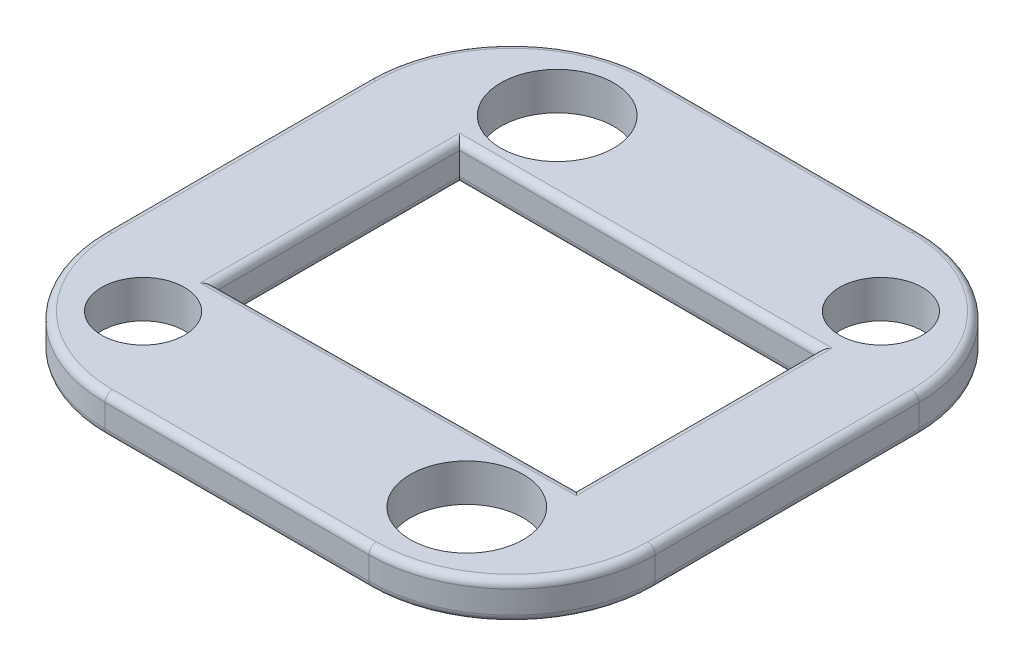
SolidWorks part; units mm, degrees
ref_plane "Front Plane" through (0, 0, 0) normal (0, 0, 1) x (1, 0, 0)
ref_plane "Top Plane" through (0, 0, 0) normal (0, 1, 0) x (1, 0, 0)
ref_plane "Right Plane" through (0, 0, 0) normal (1, 0, 0) x (0, 0, -1)
sketch "Sketch1" plane through (0, 0, 0) normal (0, 1, 0) x (1, 0, 0)
  line L0 (27.0139, 60) -> (54.7461, 60)
  line L1 (20, 0) -> (55, 0)
  line L2 (0, 20) -> (0, 55)
  line L3 (20, 75) -> (55, 75)
  line L4 (75, 20) -> (75, 55)
  line L5 (5, 60) -> (8.9861, 60)
  line L6 (5, 60) -> (5, 15)
  line L7 (5, 15) -> (5.7861, 15)
  line L8 (70, 60) -> (70, 15)
  line L9 (69.2139, 60) -> (70, 60)
  line L10 (66.0139, 15) -> (70, 15)
  line L11 (20.2539, 15) -> (47.9861, 15)
  circle A0 centre (18, 63) radius 7.5
  circle A1 centre (13.02, 13.02) radius 5.5
  circle A2 centre (61.98, 61.98) radius 5.5
  circle A3 centre (57, 12) radius 7.5
  arc A8 (8.9861, 60) -> (27.0139, 60) centre (18, 63) ccw
  arc A9 (54.7461, 60) -> (69.2139, 60) centre (61.98, 61.98) ccw
  arc A10 (66.0139, 15) -> (47.9861, 15) centre (57, 12) ccw
  arc A11 (20.2539, 15) -> (5.7861, 15) centre (13.02, 13.02) ccw
  arc A12 (55, 75) -> (75, 55) centre (55, 55) cw
  arc A13 (55, 0) -> (75, 20) centre (55, 20) ccw
  arc A14 (20, 0) -> (0, 20) centre (20, 20) cw
  arc A15 (0, 55) -> (20, 75) centre (20, 55) cw
  point P19 (75, 0)
  point P22 (0, 0)
  point P25 (0, 75)
  dimension "D5" = 11
  dimension "D8" = 15
  dimension "D11" = 11
  dimension "D12" = 15
  dimension "D15" = 20
  dimension "D20" = 2
  dimension "D21" = 2
  dimension "D22" = 2
  dimension "D23" = 2
  dimension "D24" = 11
  dimension "D1" = 75
  dimension "D2" = 75
  dimension "D3" = 13.02
  dimension "D4" = 13.02
  dimension "D6" = 18
  dimension "D7" = 12
  dimension "D9" = 13.02
  dimension "D10" = 13.02
  dimension "D13" = 12
  dimension "D14" = 18
  dimension "D16" = 5
  dimension "D17" = 5
  dimension "D18" = 15
  dimension "D19" = 15
extrude "Boss-Extrude2" add sketch "Sketch1" along normal blind 5
sketch "Sketch2" plane through (0, 5, 0) normal (0, 1, 0) x (1, 0, 0)
  line L0 (5, 15) -> (5, 60)
  line L1 (5, 60) -> (8.9861, 60)
  line L2 (69.2139, 60) -> (70, 60)
  line L3 (70, 60) -> (70, 15)
  line L4 (70, 15) -> (66.0139, 15)
  line L5 (13.02, 54.9099) -> (13.02, 20.52)
  line L6 (61.98, 54.48) -> (61.98, 20.0901)
  arc A0 (66.0139, 15) -> (47.9861, 15) centre (57, 12) ccw construction
  arc A1 (20.2539, 15) -> (5.7861, 15) centre (13.02, 13.02) ccw construction
  arc A2 (8.9861, 60) -> (27.0139, 60) centre (18, 63) ccw construction
  arc A3 (54.7461, 60) -> (69.2139, 60) centre (61.98, 61.98) ccw construction
  arc A4 (66.0139, 15) -> (61.98, 20.0901) centre (57, 12) ccw
  arc A5 (13.02, 20.52) -> (5.7861, 15) centre (13.02, 13.02) ccw
  arc A6 (8.9861, 60) -> (13.02, 54.9099) centre (18, 63) ccw
  arc A7 (61.98, 54.48) -> (69.2139, 60) centre (61.98, 61.98) ccw
  dimension "D1" = 8.02
extrude "Boss-Extrude3" add sketch "Sketch2" against normal blind 5 contours L4 A4 L6 A7 L2 L3
sketch "Sketch3" plane through (0, 5, 0) normal (0, 1, 0) x (1, 0, 0)
  line L0 (5, 60) -> (5, 15) construction
  line L1 (5, 53.5) -> (61.98, 53.5)
  line L7 (61.98, 54.48) -> (61.98, 20.0901) construction
  line L8 (54.7461, 60) -> (27.0139, 60) construction
  line L9 (8.9861, 60) -> (5, 60) construction
  line L12 (5, 60) -> (5, 53.5)
  line L13 (61.98, 54.48) -> (61.98, 53.5)
  line L14 (54.7461, 60) -> (27.0139, 60)
  line L15 (8.9861, 60) -> (5, 60)
  line L16 (61.98, 21.5505) -> (5, 20.9782)
  line L17 (5, 15) -> (5, 20.9782)
  line L18 (61.98, 21.5505) -> (61.98, 17.608)
  line L19 (8.9861, 60) -> (11.1261, 60)
  line L20 (54.7461, 60) -> (56.8488, 60)
  line L21 (61.98, 56.48) -> (61.98, 53.5)
  line L22 (47.9861, 15) -> (50.1261, 15)
  line L23 (47.9861, 15) -> (18.1512, 15)
  line L24 (7.8888, 15) -> (5, 15)
  line L26 (24.8739, 60) -> (27.0139, 60)
  circle A8 centre (13.02, 13.02) radius 5.5 construction
  circle A9 centre (57, 12) radius 7.5 construction
  circle A10 centre (61.98, 61.98) radius 5.5 construction
  circle A11 centre (18, 63) radius 7.5 construction
  arc A12 (18.1512, 15) -> (7.8888, 15) centre (13.02, 13.02) ccw
  arc A13 (61.98, 17.608) -> (50.1261, 15) centre (57, 12) ccw
  arc A14 (56.8488, 60) -> (61.98, 56.48) centre (61.98, 61.98) ccw
  arc A15 (11.1261, 60) -> (24.8739, 60) centre (18, 63) ccw
  dimension "D5" = 9.5
  dimension "D1" = 56.98
  dimension "D2" = 6.5
  dimension "D3" = 0.575
  dimension "D4" = 3.9425
  dimension "D6" = 12.3652
extrude "Boss-Extrude4" add sketch "Sketch3" against normal blind 5 contours L21 A14 L20 L14 L26 A15 L19 L15 L12 L1 | L24 L17 L16 L18 A13 L22 L23 A12
sketch "Sketch4" plane through (0, 5, 0) normal (0, 1, 0) x (1, 0, 0)
  line L10 (5, 54.5995) -> (14.5466, 54.5995)
  line L11 (5, 54.5995) -> (5, 19.8387)
  line L12 (5, 19.8387) -> (14.5466, 19.8387)
  line L13 (14.5466, 54.5995) -> (14.5466, 19.8387)
  dimension "D1" = 9.5466
  dimension "D2" = 19.8387
  dimension "D3" = 54.5995
  dimension "D4" = 14.5466
extrude "Boss-Extrude7" add sketch "Sketch4" against normal blind 5
sketch "Sketch5" plane through (0, 5, 0) normal (0, 1, 0) x (1, 0, 0)
  line L0 (55, 75) -> (20, 75) construction
  line L1 (75, 20) -> (75, 55) construction
  line L2 (20, 0) -> (55, 0) construction
  line L3 (0, 55) -> (0, 20) construction
  line L4 (55, 75) -> (20, 75)
  line L5 (75, 20) -> (75, 55)
  line L6 (20, 0) -> (55, 0)
  line L7 (0, 55) -> (0, 20)
  line L8 (1, 55) -> (1, 20)
  line L9 (20, 1) -> (55, 1)
  line L10 (74, 20) -> (74, 55)
  line L11 (55, 74) -> (20, 74)
  arc A0 (75, 55) -> (55, 75) centre (55, 55) ccw construction
  arc A1 (55, 0) -> (75, 20) centre (55, 20) ccw construction
  arc A2 (0, 20) -> (20, 0) centre (20, 20) ccw construction
  arc A3 (20, 75) -> (0, 55) centre (20, 55) ccw construction
  arc A4 (75, 55) -> (55, 75) centre (55, 55) ccw
  arc A5 (55, 0) -> (75, 20) centre (55, 20) ccw
  arc A6 (0, 20) -> (20, 0) centre (20, 20) ccw
  arc A7 (20, 75) -> (0, 55) centre (20, 55) ccw
  arc A8 (20, 74) -> (1, 55) centre (20, 55) ccw
  arc A9 (1, 20) -> (20, 1) centre (20, 20) ccw
  arc A10 (55, 1) -> (74, 20) centre (55, 20) ccw
  arc A11 (74, 55) -> (55, 74) centre (55, 55) ccw
  dimension "D1" = 1
extrude "Cut-Extrude1" cut sketch "Sketch5" against normal blind 16
fillet "Fillet4" radius 1 23 edges at (37.5, 0, -74) (6.565, 0, -68.435) (1, 0, -37.5) (6.565, 0, -6.565) (37.5, 0, -1) (68.435, 0, -6.565) (74, 0, -37.5) (74, 5, -37.5) (68.435, 5, -6.565) (37.5, 5, -1) (6.565, 5, -6.565) (1, 5, -37.5) (6.565, 5, -68.435) (37.5, 5, -74) (61.98, 5, -37.5252) (38.2633, 5, -21.3123) (14.5466, 5, -37.2871) (14.5466, 0, -37.2871) (38.2633, 0, -21.3123) (61.98, 0, -37.5252) (68.435, 0, -68.435) (68.435, 5, -68.435) (38.2633, 5, -53.5)
fillet "Fillet5" radius 1 1 edges at (38.2633, 0, -53.5)
